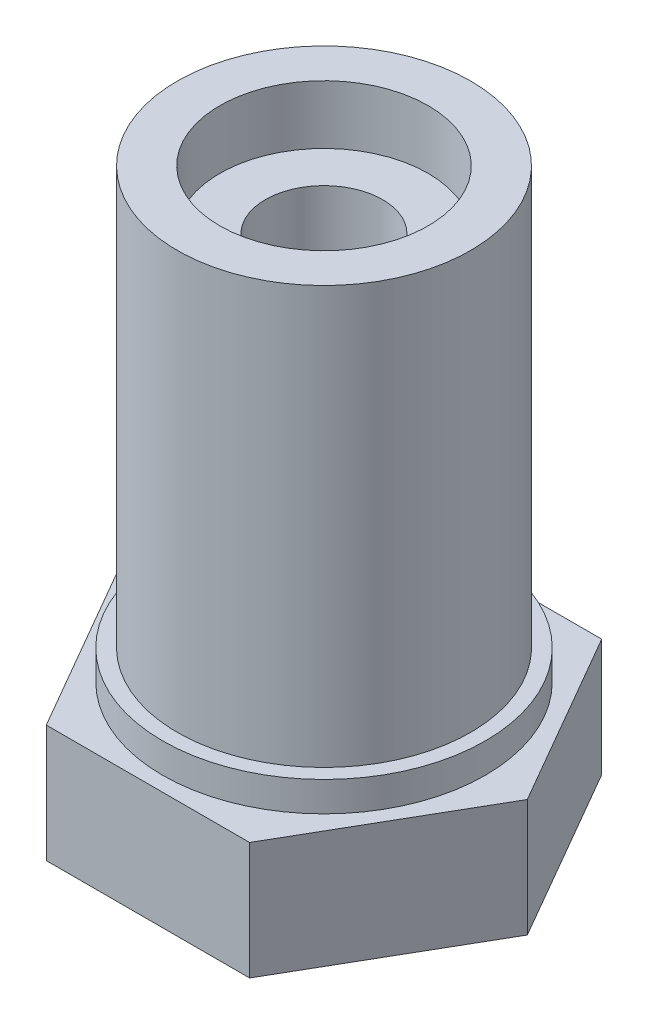
SolidWorks part; units mm, degrees
ref_plane "Front Plane" through (0, 0, 0) normal (0, 0, 1) x (1, 0, 0)
ref_plane "Top Plane" through (0, 0, 0) normal (0, 1, 0) x (1, 0, 0)
ref_plane "Right Plane" through (0, 0, 0) normal (1, 0, 0) x (0, 0, -1)
sketch "Sketch1" plane through (0, 0, 0) normal (0, 1, 0) x (1, 0, 0)
  line L1 (3.4641, 6) -> (-3.4641, 6)
  line L2 (-3.4641, 6) -> (-6.9282, 0)
  line L3 (-6.9282, 0) -> (-3.4641, -6)
  line L4 (-3.4641, -6) -> (3.4641, -6)
  line L5 (3.4641, -6) -> (6.9282, 0)
  line L6 (6.9282, 0) -> (3.4641, 6)
  circle A0 centre (0, 0) radius 6 construction
  dimension "D1" = 12
extrude "Boss-Extrude1" add sketch "Sketch1" along normal blind 4
sketch "Sketch2" plane through (0, 4, 0) normal (0, 1, 0) x (1, 0, 0)
  circle A0 centre (0, 0) radius 5
  circle A1 centre (0, 0) radius 5.5
  dimension "D1" = 11
  dimension "D2" = 10
extrude "Boss-Extrude2" add sketch "Sketch2" along normal blind 1.016
extrude "Boss-Extrude3" add sketch "Sketch2<2>" along normal blind 15.24 contours A0 region at (0, 4, 0)
sketch "Sketch2<2>" plane through (0, 4, 0) normal (0, 1, 0) x (1, 0, 0) same geometry as "Sketch2"
sketch "Sketch4" plane through (0, 19.24, 0) normal (0, 1, 0) x (1, 0, 0)
  circle A0 centre (0, 0) radius 3.55
  circle A1 centre (0, 0) radius 2
  dimension "D1" = 7.1
  dimension "D2" = 4
extrude "Cut-Extrude2" cut sketch "Sketch4" against normal through all contours A1 region at (0, 19.24, 0)
extrude "Cut-Extrude3" cut sketch "Sketch4<3>" against normal blind 2
sketch "Sketch4<3>" plane through (0, 19.24, 0) normal (0, 1, 0) x (1, 0, 0) same geometry as "Sketch4"
